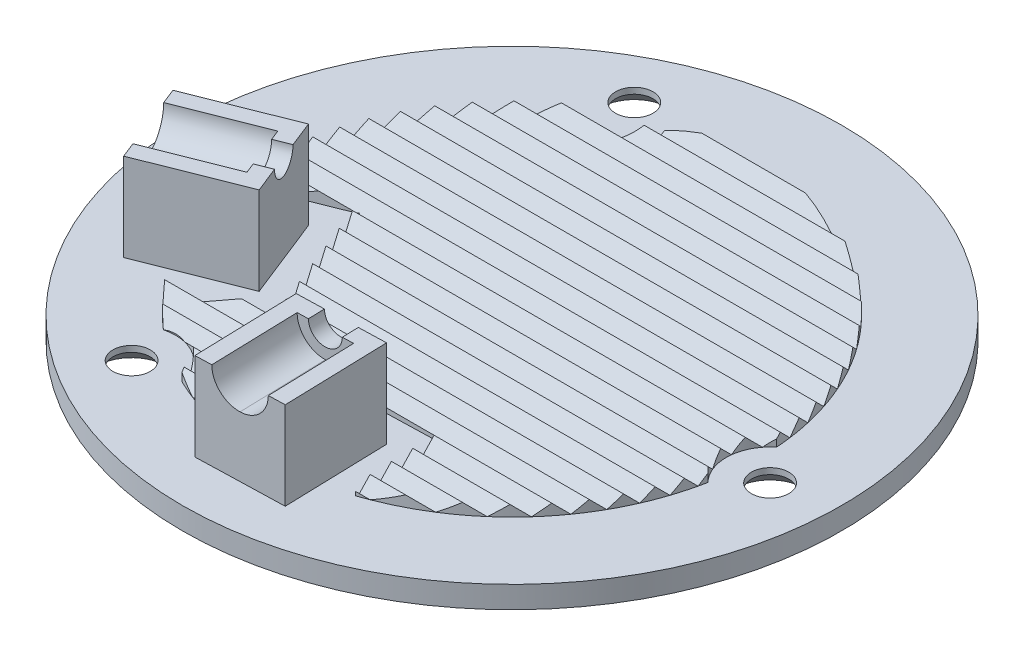
SolidWorks part; units mm, degrees
ref_plane "Front Plane" through (0, 0, 0) normal (0, 0, 1) x (1, 0, 0)
ref_plane "Top Plane" through (0, 0, 0) normal (0, 1, 0) x (1, 0, 0)
ref_plane "Right Plane" through (0, 0, 0) normal (1, 0, 0) x (0, 0, -1)
sketch "Sketch1" plane through (0, 0, 0) normal (0, 1, 0) x (1, 0, 0)
  line L1 (-30, 30) -> (30, 30)
  line L2 (-30, 30) -> (-30, -30)
  line L3 (-30, -30) -> (30, -30)
  line L4 (30, 30) -> (30, -30)
  circle A0 centre (0, 0) radius 30 construction
  dimension "D1" = 60
extrude "Boss-Extrude1" add sketch "Sketch1" along normal blind 2
sketch "Sketch2" plane through (0, 2, 0) normal (0, 1, 0) x (1, 0, 0)
  line L0 (-30, 0) -> (30, 0) construction
  line L1 (-30, 30) -> (-30, -30) construction
  line L2 (30, -30) -> (30, 30) construction
  line L3 (-30, -1) -> (30, -1)
  line L4 (-30, 1) -> (30, 1)
  line L5 (-30, 1) -> (-30, -1)
  line L6 (30, 1) -> (30, -1)
  dimension "D1" = 1
  dimension "D2" = 1
extrude "Boss-Extrude2" add sketch "Sketch2" along normal blind 1 draft 45
pattern_linear "LPattern1" count 15 spacing 2 along (0, 0, -1) count 15 spacing 2 along (0, 0, 1) of "Boss-Extrude2"
sketch "Sketch3" plane through (0, 0, 0) normal (0, -1, 0) x (1, 0, 0)
  line L0 (30, -30) -> (-30, -30) construction
  circle A0 centre (0, 0) radius 30
extrude "Cut-Extrude1" cut sketch "Sketch3" against normal blind 3 flip side to cut
ref_plane "Plane1" through (0, 2, 0) normal (0, -1, 0) x (-1, 0, 0)
sketch "Sketch4" plane through (0, 2, 0) normal (0, -1, 0) x (-1, 0, 0)
  circle A0 centre (0, 0) radius 22.5
  dimension "D1" = 45
extrude "Cut-Extrude2" cut sketch "Sketch4" against normal blind 1 flip side to cut
sketch "Sketch5" plane through (0, 0, 0) normal (0, -1, 0) x (1, 0, 0)
  line L1 (-25.177, 5.6896) -> (-16.3471, 2.1848) construction
  line L7 (-13.3957, 9.6205) -> (-22.2256, 13.1253) construction
  line L13 (-25.177, 5.6896) -> (-16.3471, 2.1848)
  line L19 (-13.3957, 9.6205) -> (-22.2256, 13.1253)
  line L24 (-13.3957, 9.6205) -> (-16.3471, 2.1848)
  line L25 (-25.177, 5.6896) -> (-22.2256, 13.1253)
extrude "Boss-Extrude4" add sketch "Sketch5" against normal blind 10
sketch "Sketch6" plane through (0, 10, 0) normal (0, 1, 0) x (1, 0, 0)
  line L5 (-17.1879, -4.1324) -> (-24.6236, -7.0838) construction
  line L9 (-22.779, -11.7311) -> (-15.3433, -8.7797) construction
  line L17 (-17.1879, -4.1324) -> (-24.6236, -7.0838)
  line L21 (-22.779, -11.7311) -> (-15.3433, -8.7797)
  line L30 (-17.1879, -4.1324) -> (-15.3433, -8.7797)
  line L34 (-22.779, -11.7311) -> (-24.6236, -7.0838)
extrude "Cut-Extrude5" cut sketch "Sketch6" against normal blind 2.5
fillet "Fillet1" radius 2.5 2 edges at (-20.9057, 7.5, 5.6081) (-19.0611, 7.5, 10.2554)
sketch "Sketch9" plane through (-16.2656, 0, 6.4561) normal (-0.9295, 0, 0.3689) x (0.3689, 0, 0.9295)
  line L0 (2.5, 10) -> (-2.5, 10) construction
  circle A0 centre (0, 10) radius 1.5
  dimension "D1" = 3
extrude "Cut-Extrude8" cut sketch "Sketch9" against normal blind 2.5
pattern_circular "CirPattern7" count 2 every 70 about axis through (0, 0, 0) along (0, 1, 0) of "Cut-Extrude8", "Fillet1", "Cut-Extrude5", "Boss-Extrude4"
sketch "Sketch10" plane through (0, 0, 0) normal (0, -1, 0) x (1, 0, 0)
  circle A1 centre (-11.2131, -22.3443) radius 2.1
  circle A2 centre (-11.2131, -22.3443) radius 2.1
  circle A3 centre (-13.7442, 20.8829) radius 2.1
  circle A4 centre (-13.7442, 20.8829) radius 2.1
  circle A5 centre (24.9573, 1.4614) radius 2.1
  circle A6 centre (24.9573, 1.4614) radius 2.1
  dimension "D1" = 0
  dimension "D2" = 0
  dimension "D3" = 0
hole_wizard "CSK for M3 Cross Recess Flat Head Screw1" positions "Sketch13" profile "Sketch15" countersink size "M3" standard "IS"
sketch "Sketch13" plane through (0, 0, 0) normal (0, -1, 0) x (-1, 0, 0)
  point P0 (11.2131, 22.3443)
  point P3 (13.7442, -20.8829)
  point P6 (-24.9573, -1.4614)
sketch "Sketch15" plane through (-11.2131, 0, -22.3443) normal (1, 0, 0) x (0, 0, -1)
  line L0 (0, 0) -> (0, 14.0215)
  line L1 (0, 14.0215) -> (1.7, 13)
  line L2 (1.7, 13) -> (1.7, 1.45)
  line L3 (1.7, 1.45) -> (3.15, 0)
  line L5 (3.15, 0) -> (0, 0)
  line L6 (-1.7, 1.45) -> (-3.15, 0) construction
  line L10 (0, 14.0215) -> (-1.7, 13) construction
  line L11 (0, -6.35) -> (0, 107.95) construction
  dimension "Hole Dia." = 3.4
  dimension "Hole Depth" = 13
  dimension "Near C'Sink Dia." = 6.3
  dimension "Near C'Sink Angle" = 90
  dimension "Drill Angle" = 118
sketch "Sketch16" plane through (0, 2, 0) normal (0, 1, 0) x (1, 0, 0)
  circle A0 centre (-11.2131, 22.3443) radius 4
  dimension "D1" = 8
extrude "Cut-Extrude9" cut sketch "Sketch16" along normal blind 2.5
pattern_circular "CirPattern8" count 3 over 360 about axis through (0, 0, 0) along (0, 1, 0) of "Cut-Extrude9"
sketch "Sketch17" plane through (0, 2, 0) normal (0, 1, 0) x (1, 0, 0)
  line L1 (-3.2646, -25.6045) -> (-3.5379, -16.1085) construction
  line L3 (4.4587, -15.8783) -> (4.7321, -25.3743) construction
  line L4 (6.8858, -13.3074) -> (-6.1088, -13.6814)
  line L5 (-3.2646, -25.6045) -> (-3.5379, -16.1085)
  line L6 (4.4587, -15.8783) -> (-3.5379, -16.1085)
  line L7 (4.4587, -15.8783) -> (4.7321, -25.3743)
  line L8 (-5.7636, -25.6765) -> (-6.1088, -13.6814)
  line L9 (7.2311, -25.3024) -> (4.7321, -25.3743)
  line L10 (-3.2646, -25.6045) -> (-5.7636, -25.6765)
  line L11 (6.8858, -13.3074) -> (7.2311, -25.3024)
  line L12 (1.8878, -13.4512) -> (6.8858, -13.3074) construction
  line L13 (1.9598, -15.9502) -> (4.4587, -15.8783) construction
  line L14 (-3.5379, -16.1085) -> (-1.039, -16.0365) construction
  line L15 (-6.1088, -13.6814) -> (-1.1109, -13.5376) construction
  dimension "D1" = 2.5
extrude "Cut-Extrude10" cut sketch "Sketch17" along normal blind 2
pattern_circular "CirPattern9" count 2 every 70 about axis through (0, 0, 0) along (0, 1, 0) of "Cut-Extrude10"
